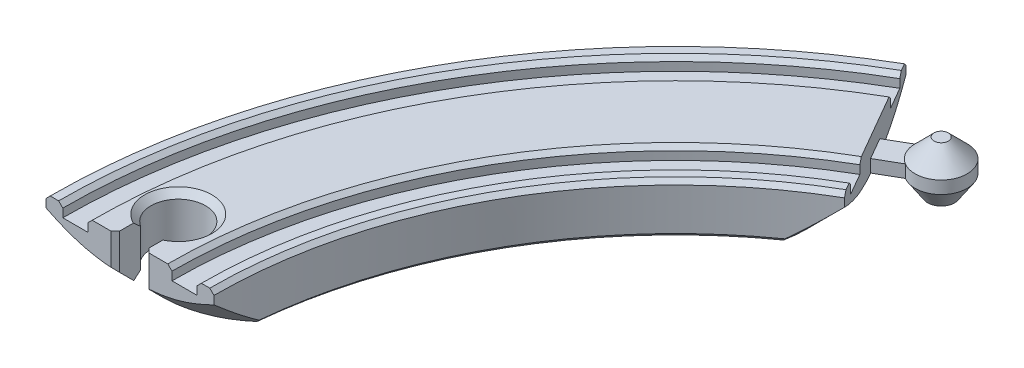
SolidWorks part; units mm, degrees
ref_plane "Front Plane" through (0, 0, 0) normal (0, 0, 1) x (1, 0, 0)
ref_plane "Top Plane" through (0, 0, 0) normal (0, 1, 0) x (1, 0, 0)
ref_plane "Right Plane" through (0, 0, 0) normal (1, 0, 0) x (0, 0, -1)
sketch "Sketch2" plane through (0, 0, 0) normal (0, 0, 1) x (1, 0, 0)
  line L0 (-20, 0) -> (20, 0)
  line L1 (20, 0) -> (20, 12)
  line L2 (20, 12) -> (16, 12)
  line L3 (16, 12) -> (16, 9)
  line L4 (16, 9) -> (10, 9)
  line L5 (10, 9) -> (10, 12)
  line L6 (10, 12) -> (-10, 12)
  line L7 (-10, 12) -> (-10, 9)
  line L8 (-10, 9) -> (-16, 9)
  line L9 (-16, 9) -> (-16, 12)
  line L10 (-16, 12) -> (-20, 12)
  line L11 (-20, 12) -> (-20, 0)
  line L12 (129.9038, 0) -> (129.9038, 12)
  point P4 (0, 0)
  dimension "D1" = 40
  dimension "D2" = 12
  dimension "D3" = 3
  dimension "D4" = 4
  dimension "D5" = 6
  dimension "D6" = 129.9038
revolve "Revolve1" add sketch "Sketch2" angle 60 about L12 region at (0, 5.6351, 0) reverse direction yes
sketch "Sketch3" plane through (0, 12, 0) normal (0, 1, 0) x (1, 0, 0)
  line L0 (10, 0) -> (-10, 0) construction
  line L2 (-3.5, 0) -> (3.5, 0)
  line L3 (-3.5, 0) -> (-3.5, 11.5)
  line L4 (-3.5, 11.5) -> (3.5, 11.5)
  line L5 (3.5, 0) -> (3.5, 11.5)
  line L6 (-3.5, 0) -> (3.5, 11.5) construction
  line L7 (-3.5, 11.5) -> (3.5, 0) construction
  circle A0 centre (0, 11.5) radius 6.5
  point P4 (0, 5.75)
  point P10 (0, 0)
  line M6 (-10, 0) -> (10, 0)
  dimension "D1" = 13
  dimension "D2" = 11.5
  dimension "D3" = 7
extrude "Cut-Extrude1" cut sketch "Sketch3" against normal through all contours L5 A0 L3 L4 | L3 A0 L5 L4 | A0 L3 L5 M6 region at (0, 12, -2.6732) region at (0, 12, -12.9919) region at (0, 12, -8.4074)
sketch "Sketch4" plane through (0, 12, 0) normal (0, 1, 0) x (1, 0, 0)
  line L0 (66.4519, 109.9019) -> (63.4519, 115.0981)
  line L1 (66.4519, 109.9019) -> (76.4112, 115.6519)
  line L2 (63.4519, 115.0981) -> (73.4112, 120.8481)
  line L3 (76.4112, 115.6519) -> (73.4112, 120.8481)
  line L4 (69.9519, 103.8397) -> (59.9519, 121.1603) construction
  circle A0 centre (74.9112, 118.25) radius 6.2
  point P9 (64.9519, 112.5)
  line M6 (69.9519, 103.8397) -> (59.9519, 121.1603)
  dimension "D1" = 12.4
  dimension "D2" = 6
  dimension "D3" = 11.5
extrude "Boss-Extrude1" add sketch "Sketch4" against normal up to surface (12 mm away) contours L1 A0 L2 L3 | L2 A0 L1 L3 region at (72.3315, 12, -116.7606) region at (75.9935, 12, -118.8749) up to face at (12.4699, 0, -33.3033)
extrude "Boss-Extrude2" add sketch "Sketch4<3>" against normal blind 7.5 contours A0 L2 L1 M6 region at (67.3597, 12, -113.8902)
sketch "Sketch4<3>" plane through (0, 12, 0) normal (0, 1, 0) x (1, 0, 0) same geometry as "Sketch4"
extrude "Cut-Extrude2" cut sketch "Sketch4<5>" against normal blind 4.5 contours A0 L2 L1 M6 region at (67.3597, 12, -113.8902)
sketch "Sketch4<5>" plane through (0, 12, 0) normal (0, 1, 0) x (1, 0, 0) same geometry as "Sketch4"
chamfer "Chamfer2" distance 4.5 angle 45 1 edges at (68.7112, 12, -118.25)
chamfer "Chamfer5" distance 3 distance2 4.5 1 edges at (74.9112, 0, -124.45) first distance on face at (74.9112, 0, -124.45)
chamfer "Chamfer3" distance 1.5 angle 45 2 edges at (0, 0, -18) (0, 12, -18)
sketch "Sketch17" plane through (-33.976, 0, -58.8481) normal (-0.5, 0, -0.866) x (-0.866, 0, 0.5)
  line L0 (-118.5741, 10.5741) -> (-118.5741, 0)
  line L1 (-118.5741, 0) -> (-108, 0)
  line L2 (-108, 0) -> (-118.5741, 10.5741)
  line L4 (-83, -1.2652) -> (-83, 10.5741) construction
  dimension "D1" = 25
revolve "Cut-Revolve1" cut sketch "Sketch17" angle 90 about L4
ref_plane "Plane1" through (-32.476, 0, -56.25) normal (-0.5, 0, -0.866) x (-0.866, 0, 0.5)
mirror "Mirror1" about plane through (-32.476, 0, -56.25) normal (-0.5, 0, -0.866) of "Cut-Revolve1"
chamfer "Chamfer4" distance 4.5 angle 45 1 edges at (64.9519, 0, -112.5)
ref_plane "Plane2" through (32.476, 0, -56.25) normal (0.5, 0, -0.866) x (-0.866, 0, -0.5)
mirror "Mirror4" about plane through (32.476, 0, -56.25) normal (0.5, 0, -0.866) of "Cut-Revolve1", "Mirror1"
chamfer "Chamfer1" distance 1 angle 45 10 edges at (34.7243, 12, -54.9519) (31.2602, 12, -56.9519) (26.0641, 12, -59.9519) (8.7436, 12, -69.9519) (3.5474, 12, -72.9519) (0.0833, 12, -74.9519) (34.7243, 0, -54.9519) (0.0833, 0, -74.9519) (3.5, 8.2521, 0) (-3.5, 8.2521, 0)
